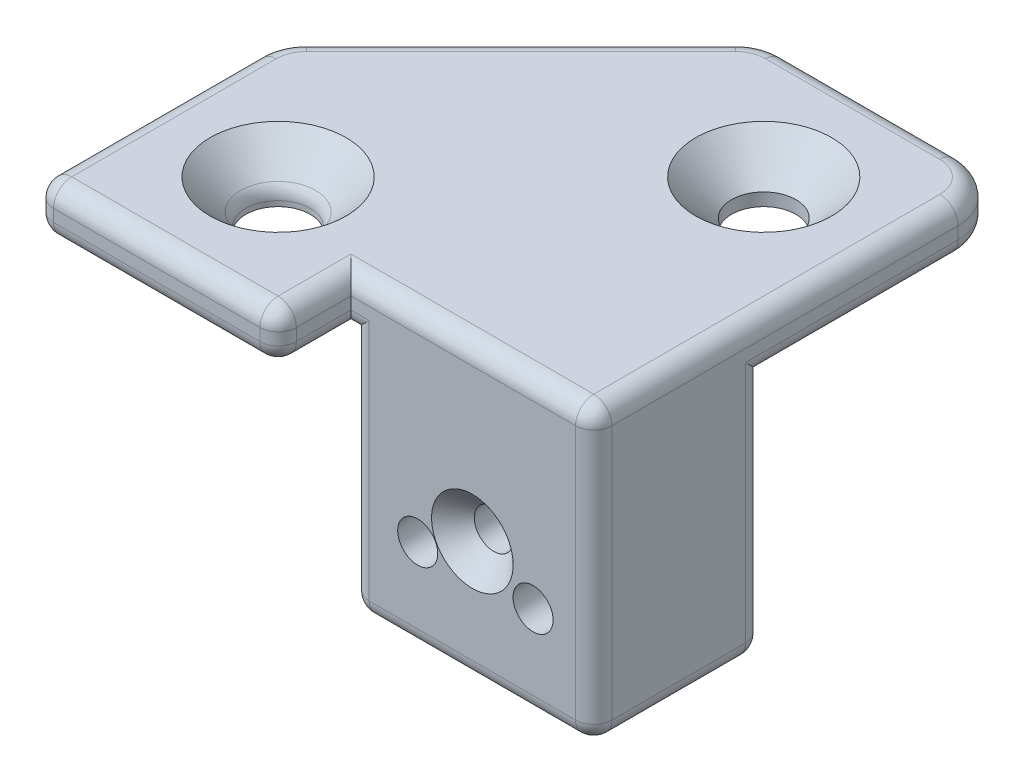
SolidWorks part; units mm, degrees
ref_plane "Front Plane" through (0, 0, 0) normal (0, 0, 1) x (1, 0, 0)
ref_plane "Top Plane" through (0, 0, 0) normal (0, 1, 0) x (1, 0, 0)
ref_plane "Right Plane" through (0, 0, 0) normal (1, 0, 0) x (0, 0, -1)
sketch "Sketch1" plane through (0, 0, 0) normal (0, 0, 1) x (1, 0, 0)
  line L1 (0, 0) -> (20, 0)
  line L2 (0, 0) -> (0, 20)
  line L3 (0, 20) -> (20, 20)
  line L4 (20, 0) -> (20, 20)
  dimension "D1" = 20
  dimension "D2" = 20
extrude "Boss-Extrude1" add sketch "Sketch1" along normal blind 14
sketch "Sketch2" plane through (0, 20, 0) normal (0, 1, 0) x (1, 0, 0)
  line L1 (0, 0) -> (20, 0)
  line L2 (0, 0) -> (0, -14)
  line L3 (0, -14) -> (20, -14)
  line L4 (20, 0) -> (20, -14)
  line L5 (0, 0) -> (-20, 0)
  line L6 (0, 0) -> (0, -20)
  line L7 (0, -20) -> (-20, -20)
  line L8 (-20, 0) -> (-20, -20)
  line L9 (20, 0) -> (0, 0)
  line L10 (20, 0) -> (20, 20)
  line L11 (20, 20) -> (0, 20)
  line L12 (0, 0) -> (0, 20)
  line M3 (20, 0) -> (0, 0)
  line M4 (0, 0) -> (0, -14)
  line M5 (0, -14) -> (20, -14)
  line M6 (20, -14) -> (20, 0)
  dimension "D1" = 20
  dimension "D2" = 20
  dimension "D3" = 20
  dimension "D4" = 20
extrude "Boss-Extrude2" add sketch "Sketch2" along normal blind 4 contours L12 L10 L11 M3 | M6 M3 M4 M5 | L5 L8 L7 L6 M4 region at (10, 20, -10) region at (10, 20, 7) region at (-10, 20, 10)
chamfer "Chamfer1" distance 20 angle 45 1 edges at (0, 22, 0)
sketch "Sketch3" plane through (0, 0, 14) normal (0, 0, 1) x (1, 0, 0)
  line L0 (5.499, 7.7) -> (14.999, 7.7)
  line L1 (0, 0) -> (20, 0) construction
  line L2 (0, 20) -> (0, 0) construction
  circle A0 centre (5.499, 7.7) radius 1.65
  circle A1 centre (14.999, 7.7) radius 1.65
  dimension "D2" = 3.3
  dimension "D3" = 3.3
  dimension "D1" = 9.5
  dimension "D4" = 7.7
  dimension "D5" = 5.499
extrude "Cut-Extrude1" cut sketch "Sketch3" against normal blind 6 contours A0 | A1 region at (14.999, 9.3033, 14) region at (3.8957, 7.7, 14)
sketch "Sketch4" plane through (0, 24, 0) normal (0, 1, 0) x (1, 0, 0)
  line L0 (20, 20) -> (0, 20) construction
  line L1 (0, 0) -> (20, 0) construction
  line L2 (0, 0) -> (0, 20) construction
  line L3 (0, 20) -> (20, 20) construction
  line L4 (20, 0) -> (20, 20) construction
  line L5 (0, 0) -> (20, 20) construction
  line L6 (0, 20) -> (20, 0) construction
  line L7 (0, 20) -> (-20, 0) construction
  line L9 (-20, 0) -> (0, 0) construction
  line L10 (-20, 0) -> (-20, -20) construction
  line L11 (-20, -20) -> (0, -20) construction
  line L12 (0, 0) -> (0, -20) construction
  line L13 (-20, 0) -> (0, -20) construction
  line L14 (-20, -20) -> (0, 0) construction
  point P0 (10, 10)
  point P12 (-10, -10)
  dimension "D1" = 20
hole_wizard "CSK for M5 SFHCS1" positions "Sketch4" profile "Sketch5" countersink size "M5" standard "ANSI Metric" end condition through all
sketch "Sketch5" plane through (10, 24, -10) normal (1, 0, 0) x (0, 0, 1)
  line L0 (0, 0) -> (0, 24)
  line L1 (0, 24) -> (2.65, 24)
  line L2 (2.65, 24) -> (2.65, 2.95)
  line L3 (2.65, 2.95) -> (5.6, 0)
  line L5 (5.6, 0) -> (0, 0)
  line L6 (-2.65, 2.95) -> (-5.6, 0) construction
  line L11 (0, -6.35) -> (0, 107.95) construction
  dimension "Thru Hole Dia." = 5.3
  dimension "Thru Hole Depth" = 24
  dimension "Near C'Sink Dia." = 11.2
  dimension "Near C'Sink Angle" = 90
hole_wizard "CSK for M3 SFHCS1" positions "3DSketch1" profile "Sketch6" countersink size "M3" standard "ANSI Metric"
sketch3d "3DSketch1"
  line L0 (0, 0, 14) -> (20, 0, 14) construction
  line L1 (0, 20, 14) -> (0, 0, 14) construction
  point P0 (10, 10, 14)
  dimension "D1" = 10
  dimension "D2" = 10
sketch "Sketch6" plane through (10, 10, 14) normal (1, 0, 0) x (0, -1, 0)
  line L0 (0, 0) -> (0, 6.9614)
  line L1 (0, 6.9614) -> (1.6, 6)
  line L2 (1.6, 6) -> (1.6, 1.76)
  line L3 (1.6, 1.76) -> (3.36, 0)
  line L5 (3.36, 0) -> (0, 0)
  line L6 (-1.6, 1.76) -> (-3.36, 0) construction
  line L10 (0, 6.9614) -> (-1.6, 6) construction
  line L11 (0, -6.35) -> (0, 107.95) construction
  dimension "Hole Dia." = 3.2
  dimension "Hole Depth" = 6
  dimension "Near C'Sink Dia." = 6.72
  dimension "Near C'Sink Angle" = 90
  dimension "Drill Angle" = 118
fillet "Fillet1" radius 4 3 edges at (-20, 22, 0) (0, 22, -20) (20, 22, -20)
fillet "Fillet2" radius 1.5 29 edges at (20, 20, -8) (18.8284, 20, -18.8284) (8.8284, 20, -20) (0.1261, 20, -19.6955) (-10, 20, -10) (-19.6955, 20, 0.1261) (-20, 24, 10.8284) (-19.6955, 24, 0.1261) (-10, 24, -10) (0.1261, 24, -19.6955) (8.8284, 24, -20) (18.8284, 24, -18.8284) (0, 0, 7) (10, 0, 14) (20, 0, 7) (10, 0, 0) (-20, 22, 20) (-10, 24, 20) (0, 22, 20) (-10, 20, 20) (20, 10, 0) (0, 10, 0) (0, 20, 17) (-20, 20, 10.8284) (10, 24, 14) (20, 24, -1) (-10, 21.05, 12.65) (0, 24, 17) (20, 12, 14)
fillet "Fillet3" radius 1.5 3 edges at (0.4393, 0.4393, 13.5607) (-0.75, 20, 14) (0, 10.75, 14)
